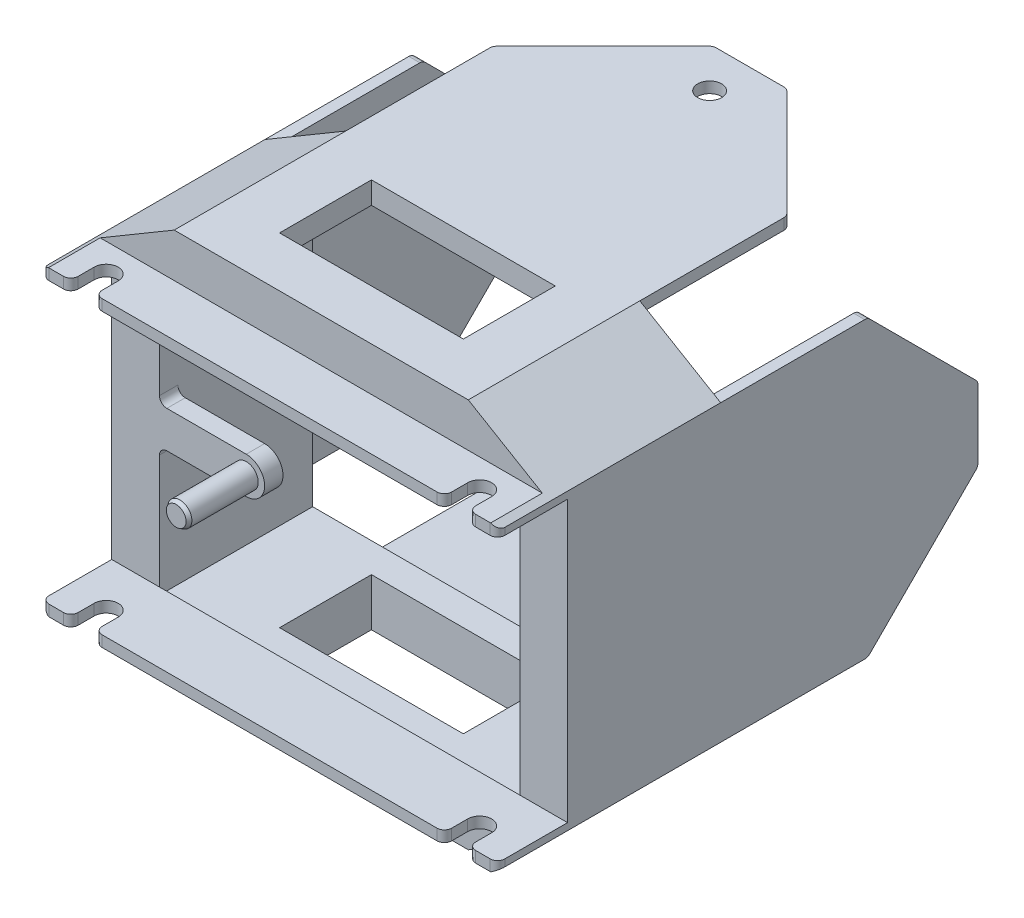
SolidWorks part; units mm, degrees
note: The reader was unsure of these and kept them because the rebuilt part matched: shared geometry of "Sketch1<6>", "Sketch4<4>", "Sketch6<3>".
ref_plane "Front Plane" through (0, 0, 0) normal (0, 0, 1) x (1, 0, 0)
ref_plane "Top Plane" through (0, 0, 0) normal (0, 1, 0) x (1, 0, 0)
ref_plane "Right Plane" through (0, 0, 0) normal (1, 0, 0) x (0, 0, -1)
sketch "Sketch1" plane through (0, 0, 0) normal (0, 0, 1) x (1, 0, 0)
  line L0 (-54.7988, -7.2731) -> (-54.7988, 82.7269) construction
  line L1 (-54.7988, 77.7269) -> (-57.7988, 77.7269)
  line L2 (-54.7988, 77.7269) -> (-54.7988, -2.2731)
  line L3 (-54.7988, -2.2731) -> (-57.7988, -2.2731)
  line L4 (-57.7988, 77.7269) -> (-57.7988, -2.2731)
  line L5 (63.2012, 82.7269) -> (63.2012, -7.2731) construction
  line L6 (63.2012, 77.7269) -> (66.2012, 77.7269)
  line L7 (63.2012, 77.7269) -> (63.2012, -2.2731)
  line L8 (63.2012, -2.2731) -> (66.2012, -2.2731)
  line L9 (66.2012, 77.7269) -> (66.2012, -2.2731)
  line L10 (-49.7988, 87.7269) -> (58.2012, 87.7269) construction
  line L11 (-35.7988, 87.7269) -> (44.2012, 87.7269)
  line L12 (-35.7988, 87.7269) -> (-35.7988, 90.7269)
  line L13 (-35.7988, 90.7269) -> (44.2012, 90.7269)
  line L14 (44.2012, 87.7269) -> (44.2012, 90.7269)
  line L15 (58.2012, -12.2731) -> (-49.7988, -12.2731) construction
  line L16 (-35.7988, -12.2731) -> (44.2012, -12.2731)
  line L17 (-35.7988, -12.2731) -> (-35.7988, -15.2731)
  line L18 (-35.7988, -15.2731) -> (44.2012, -15.2731)
  line L19 (44.2012, -12.2731) -> (44.2012, -15.2731)
  line L20 (-54.7988, 37.7269) -> (61.7012, 37.7269) construction
  line L21 (61.7012, -7.2731) -> (61.7012, 82.7269) construction
  line L22 (4.2012, 87.7269) -> (4.2012, -10.7731) construction
  line L23 (-49.7988, -10.7731) -> (58.2012, -10.7731) construction
  line L25 (-54.7988, 77.7269) -> (-44.7988, 77.7269)
  line L26 (-54.7988, 77.7269) -> (-54.7988, -2.2731)
  line L27 (-54.7988, -2.2731) -> (-44.7988, -2.2731)
  line L28 (-44.7988, 77.7269) -> (-44.7988, -2.2731)
  line L29 (63.2012, 77.7269) -> (53.2012, 77.7269)
  line L30 (63.2012, 77.7269) -> (63.2012, -2.2731)
  line L31 (63.2012, -2.2731) -> (53.2012, -2.2731)
  line L32 (53.2012, 77.7269) -> (53.2012, -2.2731)
  line L33 (-35.7988, -12.2731) -> (44.2012, -12.2731)
  line L34 (-35.7988, -12.2731) -> (-35.7988, -2.2731)
  line L35 (-35.7988, -2.2731) -> (44.2012, -2.2731)
  line L36 (44.2012, -12.2731) -> (44.2012, -2.2731)
  line L37 (-44.7988, -2.2731) -> (-35.7988, -2.2731)
  line L38 (-35.7988, -15.2731) -> (-57.7988, -2.2731)
  line L39 (44.2012, -2.2731) -> (53.2012, -2.2731)
  line L40 (66.2012, -2.2731) -> (44.2012, -15.2731)
  line L41 (-35.7988, 90.7269) -> (-57.7988, 77.7269)
  line L42 (44.2012, 84.7269) -> (53.2012, 77.7269)
  line L43 (44.2012, 90.7269) -> (66.2012, 77.7269)
  line L44 (-35.7988, 84.7269) -> (-44.7988, 77.7269)
  line L45 (-35.7988, 87.7269) -> (44.2012, 87.7269)
  line L46 (-35.7988, 87.7269) -> (-35.7988, 84.7269)
  line L47 (-35.7988, 84.7269) -> (44.2012, 84.7269)
  line L48 (44.2012, 87.7269) -> (44.2012, 84.7269)
  line L49 (14.2012, -12.2731) -> (14.2012, -15.2731)
  dimension "D1" = 3
  dimension "D2" = 10
  dimension "D3" = 80
  dimension "D4" = 80
  dimension "D5" = 3
  dimension "D6" = 10
  dimension "D7" = 10
extrude "Boss-Extrude1" add sketch "Sketch1" along normal up to surface (41.657 mm away) contours L28 L25 L2 L27 | L1 L4 L3 L2 | L46 L12 L41 L1 L25 L44 | L48 L11 L46 L47 | L11 L14 L13 L12 | L14 L48 L42 L29 L6 L43 | L29 L32 L31 L7 | L9 L6 L7 L8 | L16 L36 L35 L34 | L40 L8 L31 L39 L36 L19 | L38 L17 L34 L37 L27 L3 | L19 L16 L17 L18 | L33 L49 L18 L19
extrude "Boss-Extrude2" add sketch "Sketch1<6>" against normal blind 70 contours L9 L6 L7 L8 | L19 L16 L17 L18 | L1 L4 L3 L2 | L11 L14 L13 L12
sketch "Sketch1<6>" plane through (0, 0, 0) normal (0, 0, 1) x (1, 0, 0) same geometry as "Sketch1"
sketch "Sketch2" plane through (-57.7988, 0, 0) normal (-1, 0, 0) x (0, 0, 1)
  line L0 (-59, 37.7269) -> (-70, 37.7269) construction
  line L1 (-70, 77.7269) -> (-70, -2.2731) construction
  circle A0 centre (-59, 37.7269) radius 3.2639
  dimension "D1" = 6.5278
  dimension "D2" = 11
extrude "Cut-Extrude1" cut sketch "Sketch2" against normal up to next
sketch "Sketch3" plane through (0, 90.7269, 0) normal (0, 1, 0) x (1, 0, 0)
  line L0 (4.2012, 70) -> (4.2012, 59) construction
  line L1 (-35.7988, 70) -> (44.2012, 70) construction
  circle A0 centre (4.2012, 59) radius 3.2639
  dimension "D2" = 6.5278
  dimension "D1" = 11
extrude "Cut-Extrude2" cut sketch "Sketch3" against normal up to next
sketch "Sketch4" plane through (0, 0, 41.657) normal (0, 0, 1) x (1, 0, 0)
  line L0 (66.2012, -0.3731) -> (-57.7988, -0.3731)
  line L1 (66.2012, 77.7269) -> (66.2012, -2.2731) construction
  line L2 (-57.7988, 77.7269) -> (-57.7988, -2.2731) construction
  line L3 (-57.7988, 75.8269) -> (66.2012, 75.8269)
  line L4 (-148.1988, 75.8269) -> (156.6012, 75.8269) construction
  line L5 (-57.7988, 75.8269) -> (-57.7988, 77.7269)
  line L6 (-57.7988, 77.7269) -> (-55.9373, 78.8269)
  line L7 (-35.7988, 90.7269) -> (-57.7988, 77.7269) construction
  line L8 (-55.9373, 78.8269) -> (64.3396, 78.8269)
  line L9 (44.2012, 90.7269) -> (66.2012, 77.7269) construction
  line L10 (64.3396, 78.8269) -> (66.2012, 77.7269)
  line L11 (66.2012, 77.7269) -> (66.2012, 75.8269)
  line L12 (66.2012, -0.3731) -> (66.2012, -2.2731)
  line L13 (66.2012, -2.2731) -> (64.3396, -3.3731)
  line L14 (66.2012, -2.2731) -> (44.2012, -15.2731) construction
  line L15 (64.3396, -3.3731) -> (-55.9373, -3.3731)
  line L16 (-35.7988, -15.2731) -> (-57.7988, -2.2731) construction
  line L17 (-55.9373, -3.3731) -> (-57.7988, -2.2731)
  line L18 (-57.7988, -2.2731) -> (-57.7988, -0.3731)
  line L19 (64.3396, -3.3731) -> (44.2012, -15.2731)
  line L20 (44.2012, -15.2731) -> (-35.7988, -15.2731)
  line L21 (-35.7988, -15.2731) -> (-55.9373, -3.3731)
  line L22 (64.3396, 78.8269) -> (44.2012, 90.7269)
  line L23 (44.2012, 90.7269) -> (-35.7988, 90.7269)
  line L24 (-35.7988, 90.7269) -> (-55.9373, 78.8269)
  line M5 (66.2012, -2.2731) -> (66.2012, 77.7269)
  line M6 (66.2012, 77.7269) -> (44.2012, 90.7269)
  line M7 (44.2012, 90.7269) -> (-35.7988, 90.7269)
  line M8 (-35.7988, 90.7269) -> (-57.7988, 77.7269)
  line M9 (-57.7988, 77.7269) -> (-57.7988, -2.2731)
  line M10 (-57.7988, -2.2731) -> (-35.7988, -15.2731)
  line M11 (-35.7988, -15.2731) -> (44.2012, -15.2731)
  line M12 (44.2012, -15.2731) -> (66.2012, -2.2731)
  line M13 (-35.7988, 84.7269) -> (44.2012, 84.7269)
  line M14 (44.2012, 84.7269) -> (53.2012, 77.7269)
  line M15 (53.2012, 77.7269) -> (53.2012, -2.2731)
  line M16 (53.2012, -2.2731) -> (-44.7988, -2.2731)
  line M17 (-44.7988, -2.2731) -> (-44.7988, 77.7269)
  line M18 (-44.7988, 77.7269) -> (-35.7988, 84.7269)
  dimension "D1" = 76.2
  dimension "D2" = 3
  dimension "D3" = 3
extrude "Boss-Extrude3" add sketch "Sketch4" along normal blind 5 contours L8 M8 M18 M13 M14 M6 M7 | L8 M18 M14 M13 | L8 L3 M14 M15 M5 M6 | L8 L3 M18 M17 M15 M14 | L15 L0 M12 M5 M15 M16 M17 M9 M10 | L0 M15 M17 M16 | L15 M12 M10 M11 | L8 L3 M8 M9 M17 M18
extrude "Boss-Extrude4" add sketch "Sketch4<4>" along normal blind 19.05 contours L8 L3 M14 M15 M5 M6 | L8 L3 M18 M17 M15 M14 | L15 L0 M12 M5 M15 M16 M17 M9 M10 | L0 M15 M17 M16 | L8 L3 M8 M9 M17 M18
sketch "Sketch4<4>" plane through (0, 0, 41.657) normal (0, 0, 1) x (1, 0, 0) same geometry as "Sketch4"
sketch "Sketch5" plane through (0, -3.3731, 0) normal (0, -1, 0) x (1, 0, 0)
  line L0 (4.2012, 41.657) -> (4.2012, 54.357) construction
  line L2 (55.0012, 54.357) -> (-46.5988, 54.357) construction
  line L3 (53.2012, 41.657) -> (-44.7988, 41.657) construction
  line L4 (-49.8627, 54.357) -> (-49.8627, 60.707)
  line L5 (64.3396, 60.707) -> (-55.9373, 60.707) construction
  line L6 (-43.3349, 54.357) -> (-43.3349, 60.707)
  line L7 (-43.3349, 60.707) -> (-49.8627, 60.707)
  line L8 (51.7373, 54.357) -> (51.7373, 60.707)
  line L9 (58.2651, 54.357) -> (58.2651, 60.707)
  line L10 (58.2651, 60.707) -> (51.7373, 60.707)
  circle A0 centre (-46.5988, 54.357) radius 3.2639
  circle A1 centre (55.0012, 54.357) radius 3.2639
  point P7 (4.2012, 54.357)
  line M7 (64.3396, 46.657) -> (64.3396, 60.707)
  line M8 (64.3396, 60.707) -> (-55.9373, 60.707)
  dimension "D1" = 6.5278
  dimension "D2" = 12.7
  dimension "D3" = 101.6
extrude "Cut-Extrude3" cut sketch "Sketch5" against normal through all contours A0 L6 L4 M8 | A0 | A1 L9 L8 M8 | A1 M7
sketch "Sketch6" plane through (0, 0, 41.657) normal (0, 0, 1) x (1, 0, 0)
  line L0 (-44.7988, 37.7269) -> (-21.1988, 37.7269) construction
  line L1 (-44.7988, 75.8269) -> (-44.7988, -0.3731) construction
  line L2 (-44.7988, 37.7269) -> (-44.7988, 42.7269)
  line L3 (-44.7988, 42.7269) -> (-21.1988, 42.7269)
  line L4 (-44.7988, 37.7269) -> (-44.7988, 32.7269)
  line L5 (-44.7988, 32.7269) -> (-21.1988, 32.7269)
  line L6 (4.2012, 75.8269) -> (4.2012, -0.3731) construction
  line L9 (-21.1988, 37.7269) -> (4.2012, 37.7269) construction
  line L10 (51.7373, -0.3731) -> (-43.3349, -0.3731) construction
  line L11 (-43.3349, 75.8269) -> (51.7373, 75.8269) construction
  circle A0 centre (-21.1988, 37.7269) radius 3.2639
  arc A1 (-21.1988, 42.7269) -> (-21.1988, 32.7269) centre (-21.1988, 37.7269) cw
  point P7 (0, 0)
  point P10 (-32.9988, 32.7269)
  point P13 (62.2331, 60.9804)
  point P14 (0, 0)
  point P15 (4.2012, -0.3731)
  point P19 (4.2012, 75.8269)
  line M8 (-44.7988, -0.3731) -> (-44.7988, 75.8269)
  dimension "D1" = 6.5278
  dimension "D2" = 10
  dimension "D3" = 25.4
extrude "Boss-Extrude5" add sketch "Sketch6" against normal blind 5 contours A0 | A1 L3 L5 A0 M8
extrude "Boss-Extrude6" add sketch "Sketch6<3>" along normal blind 19.05 contours A0
sketch "Sketch6<3>" plane through (0, 0, 41.657) normal (0, 0, 1) x (1, 0, 0) same geometry as "Sketch6"
sketch "Sketch7" plane through (0, 90.7269, 0) normal (0, 1, 0) x (1, 0, 0)
  line L0 (4.2012, -46.657) -> (4.2012, -33) construction
  line L1 (29.2012, -33) -> (-20.7988, -33)
  line L2 (29.2012, -33) -> (29.2012, -8)
  line L3 (29.2012, -8) -> (-20.7988, -8)
  line L4 (-20.7988, -33) -> (-20.7988, -8)
  line L5 (44.2012, -46.657) -> (-35.7988, -46.657) construction
  dimension "D1" = 25
  dimension "D2" = 50
  dimension "D3" = 8
extrude "Cut-Extrude4" cut sketch "Sketch7" against normal through all
chamfer "Chamfer1" distance 30 angle 45 8 edges at (-56.2988, 77.7269, -70) (-56.2988, -2.2731, -70) (-35.7988, -13.7731, -70) (14.2012, -13.7731, -70) (64.7012, -2.2731, -70) (64.7012, 77.7269, -70) (44.2012, 89.2269, -70) (-35.7988, 89.2269, -70)
chamfer "Chamfer2" distance 1 angle 30 1 edges at (-17.9349, 37.7269, 60.707)
fillet "Fillet1" radius 2 33 edges at (65.2704, -2.8231, 60.707) (66.2012, -1.3231, 60.707) (-57.7988, -1.3231, 60.707) (-56.8681, -2.8231, 60.707) (-56.8681, 78.2769, 60.707) (-57.7988, 76.7769, 60.707) (66.2012, 76.7769, 60.707) (65.2704, 78.2769, 60.707) (58.2651, 77.3269, 60.707) (51.7373, 77.3269, 60.707) (-43.3349, 77.3269, 60.707) (-49.8627, 77.3269, 60.707) (-49.8627, -1.8731, 60.707) (-43.3349, -1.8731, 60.707) (51.7373, -1.8731, 60.707) (58.2651, -1.8731, 60.707) (-44.7988, 32.7269, 39.157) (-44.7988, 42.7269, 39.157) (14.2012, 89.2269, -70) (-5.7988, 89.2269, -70) (-35.7988, 89.2269, -40) (-56.2988, 77.7269, -40) (-56.2988, 27.7269, -70) (-56.2988, 47.7269, -70) (-56.2988, -2.2731, -40) (-35.7988, -13.7731, -40) (14.2012, -13.7731, -40) (64.7012, -2.2731, -40) (64.7012, 47.7269, -70) (64.7012, 27.7269, -70) (64.7012, 77.7269, -40) (44.2012, 89.2269, -40) (-10.7988, -13.7731, -65)
